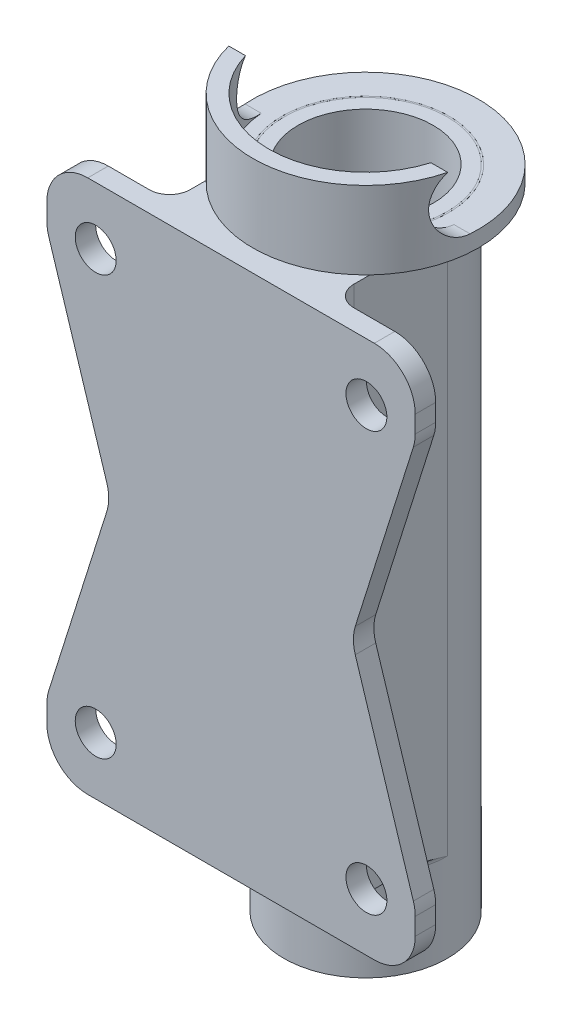
SolidWorks part; units mm, degrees
note: The reader was unsure of these and kept them because the rebuilt part matched: shared geometry of "Sketch26<3>".
other "shoe_support"
other "pipe"
other "angle_limit"
other "Weld Folder"
material "6061 Alloy"
ref_plane "Front Plane" through (0, 0, 0) normal (0, 0, 1) x (1, 0, 0)
ref_plane "Top Plane" through (0, 0, 0) normal (0, 1, 0) x (1, 0, 0)
ref_plane "Right Plane" through (0, 0, 0) normal (1, 0, 0) x (0, 0, -1)
sketch "Sketch11" plane through (0, 0, 0) normal (0, 0, 1) x (1, 0, 0)
  line L0 (0, 0) -> (0, 109.6398) construction
  line L1 (0, 0) -> (-89.1372, 0) construction
sketch "Sketch12" plane through (0, 0, 0) normal (0, 0, 1) x (1, 0, 0)
  line L0 (-25.4, 0) -> (-25.4, 203.2)
  line L1 (200000, 0) -> (-200089.1372, 0) construction
  line L4 (-20.955, 0) -> (-25.4, 0)
  line L5 (-20.955, 0) -> (-20.955, 38.1)
  line L6 (-20.955, 38.1) -> (-19.177, 38.1)
  line L7 (-19.177, 38.1) -> (-19.177, 165.1)
  line L8 (-19.177, 165.1) -> (-20.955, 165.1)
  line L9 (-20.955, 165.1) -> (-20.955, 203.2)
  line L10 (-20.955, 203.2) -> (-25.4, 203.2)
  line L12 (0, -200000) -> (0, 200109.6398) construction
  line L13 (-20.955, 203.2) -> (-15.875, 203.2) construction
  line L14 (-15.875, 203.2) -> (-15.875, 0) construction
  line L15 (-15.875, 0) -> (-20.955, 0) construction
  dimension "D1" = 25.4
  dimension "D2" = 20.955
  dimension "D3" = 19.177
  dimension "D4" = 38.1
  dimension "D5" = 203.2
  dimension "D6" = 4.445
  dimension "D7" = 15.875
revolve "Revolve1" add sketch "Sketch12" angle 360 about L0
ref_plane "mideplane" through (0, 101.6, 0) normal (0, -1, 0) x (-1, 0, 0)
ref_plane "top pipe plane" through (0, 30, 0) normal (0, -1, 0) x (-1, 0, 0)
ref_plane "bottom pipe plane" through (0, 183.2, 0) normal (0, 1, 0) x (1, 0, 0)
ref_plane "pipe support midplane" through (0, 106.6, 0) normal (0, -1, 0) x (-1, 0, 0)
sketch "Sketch14" plane through (0, 30, 0) normal (0, -1, 0) x (-1, 0, 0)
  line L0 (0, 0) -> (-25.4, 0) construction
  line L1 (0, 0) -> (25.4, 0) construction
  line L7 (-25.4, -35.4) -> (25.4, -35.4)
  line L9 (25.4, -35.4) -> (25.4, 0)
  line L10 (-25.4, -35.4) -> (-25.4, 0)
  circle A0 centre (0, 0) radius 25.4 construction
  circle A1 centre (0, 0) radius 25.4
  circle A2 centre (0, 0) radius 25.4 construction
  arc A3 (25.4, 0) -> (-25.4, 0) centre (0, 0) cw
  dimension "D1" = 0
  dimension "D2" = 10
extrude "Boss-Extrude1" add sketch "Sketch14" against normal blind 3.175 separate body contours A1 L10 L7 L9
sketch "Sketch15" plane through (0, 33.175, 0) normal (0, 1, 0) x (1, 0, 0)
  line L0 (25.4, -35.4) -> (-25.4, -35.4) construction
  line L4 (-1.5875, -35.4) -> (1.5875, -35.4)
  line L5 (-1.5875, -35.4) -> (-1.5875, -25.3503)
  line L7 (1.5875, -35.4) -> (1.5875, -25.3503)
  circle A1 centre (0, 0) radius 25.4 construction
  circle A2 centre (0, 0) radius 25.4
  dimension "D1" = 3.175
extrude "Boss-Extrude4" add sketch "Sketch15" along normal up to surface (150.025 mm away) contours A2 L5 L4 L7 up to plane "bottom pipe plane"
sketch "Sketch17" plane through (0, 183.2, 0) normal (0, 1, 0) x (1, 0, 0)
  line L3 (25.4, -35.4) -> (25.4, 0)
  line L4 (-25.4, -35.4) -> (25.4, -35.4)
  line L5 (-25.4, 0) -> (-25.4, -35.4)
  line L9 (25.4, -35.4) -> (25.4, 0)
  line L10 (-25.4, -35.4) -> (25.4, -35.4)
  line L11 (-25.4, 0) -> (-25.4, -35.4)
  arc A1 (-25.4, 0) -> (25.4, 0) centre (0, 0) ccw
  arc A3 (-25.4, 0) -> (25.4, 0) centre (0, 0) ccw
  dimension "D1" = 0
extrude "Boss-Extrude5" add sketch "Sketch17" along normal blind 3.175
sketch "Sketch18" plane through (0, 0, 35.4) normal (0, 0, 1) x (1, 0, 0)
  line L1 (57.15, 30) -> (-57.15, 30)
  line L2 (57.15, 30) -> (57.15, 203.2)
  line L4 (-57.15, 30) -> (-57.15, 203.2)
  line L5 (20.955, 203.2) -> (-20.955, 203.2) construction
  line L6 (-57.15, 203.2) -> (57.15, 203.2)
  line L7 (25.4, 203.2) -> (-25.4, 203.2) construction
  line L8 (0, 30) -> (0, 203.2) construction
  line L10 (46.15, 116.6) -> (-46.15, 116.6) construction
  line L11 (46.15, 47.175) -> (-46.15, 47.175) construction
  line L12 (46.15, 47.175) -> (46.15, 186.025) construction
  line L13 (46.15, 186.025) -> (-46.15, 186.025) construction
  line L14 (-46.15, 47.175) -> (-46.15, 186.025) construction
  line L15 (25.4, 30) -> (-25.4, 30) construction
  circle A0 centre (-46.15, 47.175) radius 5 construction
  circle A1 centre (-46.15, 47.175) radius 8 construction
  point P10 (46.15, 116.6)
  point P12 (-46.15, 116.6)
  point P13 (0, 203.2)
  point P21 (0, 116.6)
  line M9 (25.4, 30) -> (25.4, 33.175)
  line M19 (-25.4, 33.175) -> (-25.4, 30)
  line M35 (-25.4, 30) -> (25.4, 30)
  line M36 (25.4, 33.175) -> (1.5875, 33.175)
  line M38 (-1.5875, 33.175) -> (-25.4, 33.175)
  line M39 (1.5875, 33.175) -> (1.5875, 183.2)
  line M41 (-1.5875, 183.2) -> (-1.5875, 33.175)
  line M42 (1.5875, 183.2) -> (25.4, 183.2)
  line M43 (25.4, 183.2) -> (25.4, 186.375)
  line M44 (25.4, 186.375) -> (-25.4, 186.375)
  line M45 (-25.4, 186.375) -> (-25.4, 183.2)
  line M46 (-25.4, 183.2) -> (-1.5875, 183.2)
  dimension "D4" = 10
  dimension "D5" = 16
  dimension "D6" = 6
  dimension "D7" = 9.175
  dimension "D1" = 114.3
extrude "Boss-Extrude6" add sketch "Sketch18" along normal blind 6.35 contours L4 M38 M41 M46 | L2 M36 M42 M39 | M19 M35 M9 M36 M39 M42 M43 M44 M45 M46 M41 M38
sketch "Sketch30" plane through (0, 106.6, 0) normal (0, -1, 0) x (-1, 0, 0)
  line L3 (25.4, -35.4) -> (25.4, 0)
  line L4 (-25.4, -35.4) -> (25.4, -35.4)
  line L5 (-25.4, 0) -> (-25.4, -35.4)
  line L6 (25.4, -35.4) -> (25.4, 0)
  line L8 (-25.4, 0) -> (-25.4, -35.4)
  line L9 (-25.4, -35.4) -> (25.4, -35.4)
  arc A1 (-25.4, 0) -> (25.4, 0) centre (0, 0) ccw
  arc A2 (-25.4, 0) -> (25.4, 0) centre (0, 0) ccw
  dimension "D1" = 0
extrude "Boss-Extrude9" add sketch "Sketch30" along normal blind 1.5875 and the other way blind 1.5875
sketch "Sketch29" plane through (0, 0, 0) normal (0, -1, 0) x (1, 0, 0)
  circle A0 centre (0, 0) radius 20.955 construction
  circle A1 centre (0, 0) radius 20.955 construction
ref_plane "Plane4" through (0, 200.7, 0) normal (0, 1, 0) x (1, 0, 0)
sketch "Sketch25" plane through (0, 200.7, 0) normal (0, 1, 0) x (1, 0, 0)
  line L0 (0, -2.5) -> (34.9106, -2.5) construction
  line L1 (0, 2.5) -> (34.9106, 2.5) construction
  line L2 (0, 0) -> (35, 0) construction
  circle A0 centre (0, 0) radius 25.4 construction
  circle A1 centre (0, 0) radius 25.4 construction
  circle A2 centre (0, 0) radius 35 construction
  circle A3 centre (0, 0) radius 25.9 construction
  circle A4 centre (0, 0) radius 2.5 construction
  dimension "D1" = 0.5
  dimension "D2" = 70
  dimension "D3" = 5
sketch "Sketch26" plane through (0, 200.7, 0) normal (0, 1, 0) x (1, 0, 0)
  line L0 (34.9106, -2.5) -> (-34.9106, -2.5)
  circle A0 centre (0, 0) radius 25.9 construction
  circle A1 centre (0, 0) radius 35 construction
  circle A2 centre (0, 0) radius 25.9
  circle A3 centre (0, 0) radius 35
  arc A4 (29.8957, -2.5) -> (-29.8957, -2.5) centre (0, 0) cw
  point P0 (34.9106, -2.5)
  dimension "D1" = 5
extrude "Boss-Extrude7" add sketch "Sketch26" against normal blind 5 separate body
extrude "Boss-Extrude8" add sketch "Sketch26<3>" along normal blind 19.05 contours L0 A4 A3
sketch "Sketch26<3>" plane through (0, 200.7, 0) normal (0, 1, 0) x (1, 0, 0) same geometry as "Sketch26"
sketch "Sketch33" plane through (0, 0, 0) normal (1, 0, 0) x (0, 0, -1)
  line L0 (-2.5, 219.75) -> (-35, 219.75) construction
  line L1 (-8.5, 219.75) -> (-2.5, 219.75)
  line L3 (35, 200.7) -> (-2.5, 200.7) construction
  line L8 (-2.5, 219.75) -> (-2.5, 200.7) construction
  line L11 (-2.5, 219.75) -> (-2.5, 200.7)
  arc A1 (-2.5, 200.7) -> (-8.5, 219.75) centre (-2.5, 211.1699) cw
  dimension "D1" = 6
extrude "Cut-Extrude3" cut sketch "Sketch33" against normal through all both and the other way through all
sketch "Sketch34" plane through (0, 33.175, 0) normal (0, 1, 0) x (1, 0, 0)
  line L3 (-25.4, -35.4) -> (-1.5875, -35.4)
  line L4 (-1.5875, -35.4) -> (-1.5875, -25.3503)
  line L5 (-25.4, 0) -> (-25.4, -35.4)
  line L6 (-25.4, -35.4) -> (-1.5875, -35.4)
  line L7 (-1.5875, -35.4) -> (-1.5875, -25.3503)
  line L8 (-25.4, 0) -> (-25.4, -35.4)
  line L9 (1.5875, -25.3503) -> (1.5875, -35.4)
  line L10 (1.5875, -35.4) -> (25.4, -35.4)
  line L11 (25.4, -35.4) -> (25.4, 0)
  line L12 (1.5875, -25.3503) -> (1.5875, -35.4)
  line L13 (1.5875, -35.4) -> (25.4, -35.4)
  line L14 (25.4, -35.4) -> (25.4, 0)
  arc A1 (-25.4, 0) -> (-1.5875, -25.3503) centre (0, 0) ccw
  arc A2 (-25.4, 0) -> (-1.5875, -25.3503) centre (0, 0) ccw
  arc A3 (1.5875, -25.3503) -> (25.4, 0) centre (0, 0) ccw
  arc A4 (1.5875, -25.3503) -> (25.4, 0) centre (0, 0) ccw
  dimension "D1" = 0
  dimension "D2" = 0
extrude "Boss-Extrude10" add sketch "Sketch34" along normal up to surface (150.025 mm away) up to face at (14.7486, 183.2, 25.2163)
sketch "Sketch35" plane through (0, 186.375, 0) normal (0, 1, 0) x (1, 0, 0)
  line L5 (-25.4, -35.4) -> (25.4, -35.4)
  line L6 (-25.4, -35.4) -> (25.4, -35.4)
  line L10 (25.4, -35.4) -> (25.4, 0)
  line L11 (-25.4, 0) -> (-25.4, -35.4)
  line L17 (25.4, -35.4) -> (25.4, 0)
  line L18 (-25.4, 0) -> (-25.4, -35.4)
  arc A4 (-25.4, 0) -> (25.4, 0) centre (0, 0) ccw
  arc A7 (-25.4, 0) -> (25.4, 0) centre (0, 0) ccw
  dimension "D1" = 0
extrude "Boss-Extrude11" add sketch "Sketch35" along normal up to surface (9.325 mm away) up to face at (0, 195.7, 25.9)
sketch "Sketch36" plane through (57.15, 0, 0) normal (1, 0, 0) x (0, 0, -1)
  line L0 (-41.75, 30) -> (-41.75, 203.2) construction
  line L1 (-35.4, 203.2) -> (-41.75, 203.2)
  line L2 (-35.4, 203.2) -> (-35.4, 195.7)
  line L3 (-35.4, 195.7) -> (-41.75, 195.7)
  line L4 (-41.75, 203.2) -> (-41.75, 195.7)
  line L5 (-35.4, 195.7) -> (-24.0799, 195.7) construction
extrude "Cut-Extrude4" cut sketch "Sketch36" against normal through all
fillet "Fillet1" radius 6.35 2 edges at (-25.4, 112.85, 35.4) (25.4, 112.85, 35.4)
sketch "Sketch37" plane through (0, 0, 35.4) normal (0, 0, -1) x (-1, 0, 0)
  line L0 (0, 30) -> (0, 195.7) construction
  line L1 (-35, 195.7) -> (35, 195.7) construction
  line L2 (-57.15, 112.85) -> (57.15, 112.85) construction
  line L3 (-57.15, 30) -> (-57.15, 195.7) construction
  line L4 (57.15, 30) -> (57.15, 195.7) construction
  line L5 (-57.15, 175.7) -> (-37.3335, 112.85)
  line L6 (-57.15, 175.7) -> (-57.15, 50)
  line L8 (-57.15, 50) -> (-37.3335, 112.85)
  line L9 (57.15, 50) -> (37.3335, 112.85)
  line L11 (57.15, 175.7) -> (57.15, 50)
  line L12 (57.15, 175.7) -> (37.3335, 112.85)
  dimension "D1" = 20
  dimension "D2" = 17.5
extrude "Cut-Extrude5" cut sketch "Sketch37" against normal through all contours L12 L11 L9 | L5 L6 L8
fillet "Fillet2" radius 12.7 10 edges at (-57.15, 195.7, 38.575) (57.15, 195.7, 38.575) (-57.15, 50, 38.575) (-37.3335, 112.85, 38.575) (-57.15, 175.7, 38.575) (37.3335, 112.85, 38.575) (57.15, 50, 38.575) (57.15, 175.7, 38.575) (-57.15, 30, 38.575) (57.15, 30, 38.575)
sketch "Sketch38" plane through (0, 0, 35.4) normal (0, 0, -1) x (-1, 0, 0)
  line L0 (0, 30) -> (0, 195.7) construction
  line L1 (-35, 195.7) -> (35, 195.7) construction
  line L5 (25.4, 30) -> (31.75, 30) construction
  line L6 (-37.9498, 112.85) -> (37.9498, 112.85) construction
  circle A0 centre (-42, 177.85) radius 6.35
  arc A8 (-38.5376, 109.031) -> (-38.5376, 116.669) centre (-50.6498, 112.85) ccw construction
  arc A9 (38.5376, 116.669) -> (38.5376, 109.031) centre (50.6498, 112.85) ccw construction
  circle A10 centre (42, 177.85) radius 6.35
  circle A11 centre (42, 47.85) radius 6.35
  circle A12 centre (-42, 47.85) radius 6.35
  dimension "D1" = 12.7
  dimension "D2" = 42
  dimension "D3" = 65
extrude "Cut-Extrude6" cut sketch "Sketch38" against normal through all
sketch "Sketch41" plane through (0, 200.7, 0) normal (0, 1, 0) x (1, 0, 0)
  circle A0 centre (0, 0) radius 25.4
  circle A1 centre (0, 0) radius 25.4 construction
extrude "Cut-Extrude8" cut sketch "Sketch41" along normal through all
surface "Surface-Fill1"
fillet "Fillet4" radius 2.5 1 edges at (0, 30, 25.4)
